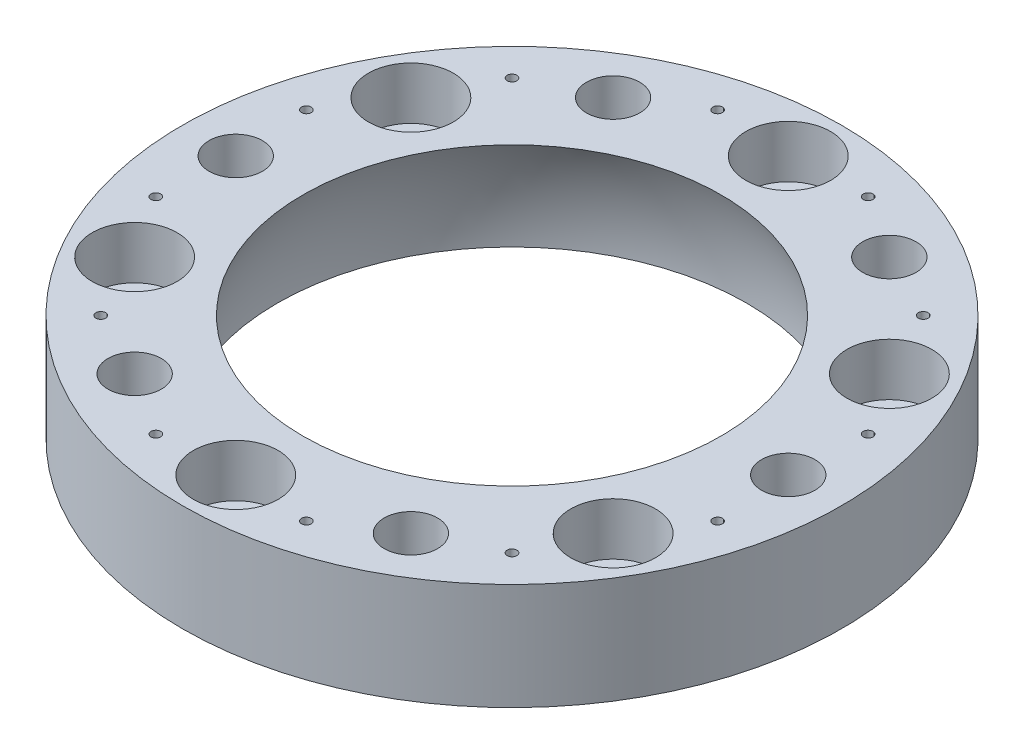
SolidWorks part; units mm, degrees
ref_plane "前视基准面" through (0, 0, 0) normal (0, 0, 1) x (1, 0, 0)
ref_plane "上视基准面" through (0, 0, 0) normal (0, 1, 0) x (1, 0, 0)
ref_plane "右视基准面" through (0, 0, 0) normal (1, 0, 0) x (0, 0, -1)
other "Configuration Table"
sketch "草图1" plane through (0, 0, 0) normal (0, 1, 0) x (1, 0, 0)
  circle A0 centre (0, 0) radius 68
  circle A2 centre (0, 57) radius 5.5
  circle A3 centre (28.5, 49.3634) radius 5.5
  circle A4 centre (49.3634, 28.5) radius 5.5
  circle A5 centre (57, 0) radius 5.5
  circle A6 centre (49.3634, -28.5) radius 5.5
  circle A7 centre (28.5, -49.3634) radius 5.5
  circle A8 centre (0, -57) radius 5.5
  circle A9 centre (-28.5, -49.3634) radius 5.5
  circle A10 centre (-49.3634, -28.5) radius 5.5
  circle A11 centre (-57, 0) radius 5.5
  circle A12 centre (-49.3634, 28.5) radius 5.5
  circle A13 centre (-28.5, 49.3634) radius 5.5
  point P30 (0, 0)
  dimension "D1" = 12
extrude "凸台-拉伸1" add sketch "草图1" along normal blind 60
sketch "草图2" plane through (0, 60, 0) normal (0, 1, 0) x (1, 0, 0)
  circle A0 centre (0, 57) radius 8.75
  circle A1 centre (49.3634, 28.5) radius 8.75
  circle A2 centre (49.3634, -28.5) radius 8.75
  circle A3 centre (0, -57) radius 8.75
  circle A4 centre (-49.3634, -28.5) radius 8.75
  circle A5 centre (-49.3634, 28.5) radius 8.75
  point P15 (0, 0)
  dimension "D1" = 6
extrude "切除-拉伸1" cut sketch "草图2" against normal blind 10.8
sketch "草图4" plane through (0, 0, 0) normal (0, -1, 0) x (1, 0, 0)
  circle A0 centre (28.5, 49.3634) radius 8.75
  circle A1 centre (57, 0) radius 8.75
  circle A2 centre (28.5, -49.3634) radius 8.75
  circle A3 centre (-28.5, -49.3634) radius 8.75
  circle A4 centre (-57, 0) radius 8.75
  circle A5 centre (-28.5, 49.3634) radius 8.75
  point P16 (0, 0)
  dimension "D1" = 6
extrude "切除-拉伸2" cut sketch "草图4" against normal blind 10.8
sketch "草图5" plane through (0, 0, 0) normal (0, -1, 0) x (1, 0, 0)
  circle A0 centre (0, 0) radius 68
extrude "切除-拉伸3" cut sketch "草图5" against normal blind 38
ref_plane "基准面1" through (0, 0, 0) normal (0, -1, 0) x (-1, 0, 0)
ref_plane "基准面2" through (0, 0, 0) normal (1, 0, 0) x (0, 0, -1)
ref_axis "基准轴1" through (0, 0, 0) along (0, -1, 0)
ref_plane "基准面3" through (0, 0, 0) normal (0, 0, -1) x (-1, 0, 0)
sketch "草图10" plane through (0, 0, 0) normal (0, 0, -1) x (-1, 0, 0)
  line L3 (0, 86.4149) -> (0, -10.4149)
  arc A0 (0, 86.4149) -> (0, -10.4149) centre (0, 38) ccw
revolve "切除-旋转6" cut sketch "草图10" angle 360 about L3
sketch "草图11" plane through (0, 60, 0) normal (0, 1, 0) x (1, 0, 0)
  circle A1 centre (15.5291, 57.9555) radius 1
  circle A2 centre (42.4264, 42.4264) radius 1
  circle A3 centre (57.9555, 15.5291) radius 1
  circle A4 centre (57.9555, -15.5291) radius 1
  circle A5 centre (42.4264, -42.4264) radius 1
  circle A6 centre (15.5291, -57.9555) radius 1
  circle A7 centre (-15.5291, -57.9555) radius 1
  circle A8 centre (-42.4264, -42.4264) radius 1
  circle A9 centre (-57.9555, -15.5291) radius 1
  circle A10 centre (-57.9555, 15.5291) radius 1
  circle A11 centre (-42.4264, 42.4264) radius 1
  circle A12 centre (-15.5291, 57.9555) radius 1
  point P18 (0, 0)
  dimension "D1" = 12
extrude "切除-拉伸4" cut sketch "草图11" against normal through all
